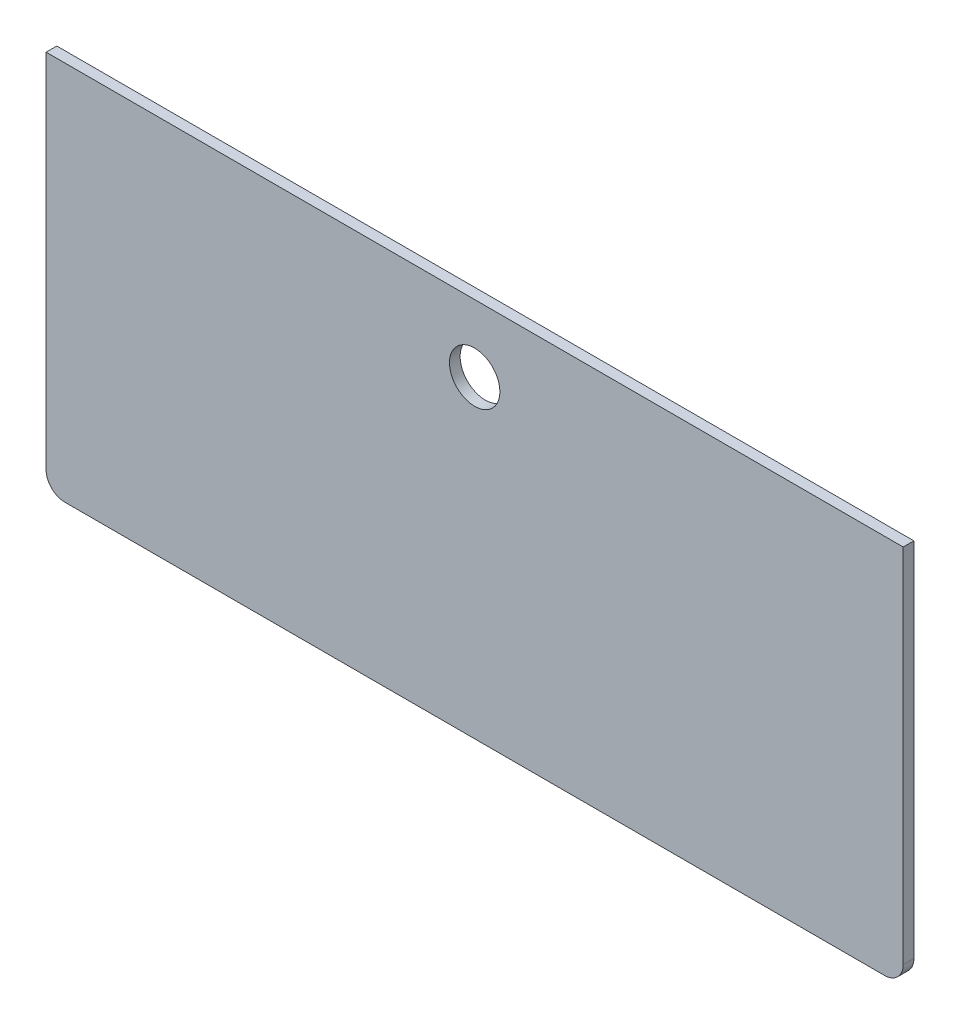
SolidWorks part; units mm, degrees
material "5052-H32"
ref_plane "Front Plane" through (0, 0, 0) normal (0, 0, 1) x (1, 0, 0)
ref_plane "Top Plane" through (0, 0, 0) normal (0, 1, 0) x (1, 0, 0)
ref_plane "Right Plane" through (0, 0, 0) normal (1, 0, 0) x (0, 0, -1)
sketch "Sketch1" plane through (0, 0, 0) normal (0, 0, 1) x (1, 0, 0)
  line L0 (-151.7654, 27.1868) -> (-151.7654, -85.9882)
  line L1 (-151.7654, -85.9882) -> (103.2346, -85.9882)
  line L2 (103.2346, -85.9882) -> (103.2346, 27.1868)
  line L3 (103.2346, 27.1868) -> (-151.7654, 27.1868)
  line L4 (-24.2654, 27.1868) -> (-24.2654, 7.1868) construction
  circle A0 centre (-24.2654, 7.1868) radius 7.5
  dimension "D4" = 15
  dimension "D1" = 113.175
  dimension "D2" = 255
  dimension "D3" = 20
extrude "Boss-Extrude1" add sketch "Sketch1" along normal blind 3.175
fillet "Fillet1" radius 5.5562 2 edges at (-151.7654, -85.9882, 1.5875) (103.2346, -85.9882, 1.5875)
equation "\"L\"= 410mm"
equation "\"W\"= 255mm"
equation "\"H\"= 110mm"
equation "\"Compartment Width\"= 80"
equation "\"T\"= 4.7625 * 2 / 3mm"
equation "\"Inside Fillet Radius\"= 5.55625mm"
equation "\"D1@Boss-Extrude1\"=\"T\""
equation "\"D1@Fillet1\"=\"Inside Fillet Radius\""
equation "\"Hole\"=15mm"
equation "\"D4@Sketch1\"=\"Hole\""
equation "\"D2@Sketch1\"=\"W\""
equation "\"D1@Sketch1\"=\"H\"+\"T\""
